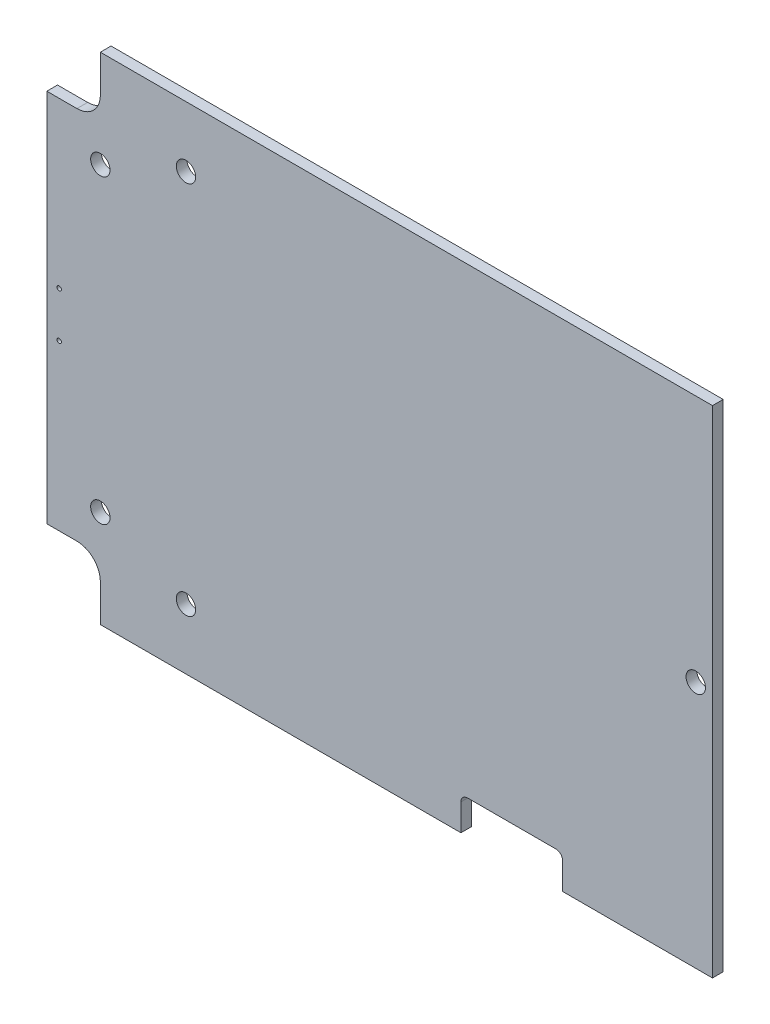
SolidWorks part; units mm, degrees
ref_plane "Płaszczyzna przednia" through (0, 0, 0) normal (0, 0, 1) x (1, 0, 0)
ref_plane "Płaszczyzna górna" through (0, 0, 0) normal (0, 1, 0) x (1, 0, 0)
ref_plane "Płaszczyzna prawa" through (0, 0, 0) normal (1, 0, 0) x (0, 0, -1)
sketch "Sketch1" plane through (0, 0, 0) normal (0, 0, 1) x (1, 0, 0)
  line L7 (246.9504, 63.2305) -> (246.9504, 62.5305) construction
  line L8 (246.9504, 62.5305) -> (245.4504, 62.5305) construction
  line L9 (245.4504, -11.1695) -> (246.9504, -11.1695) construction
  line L10 (246.9504, -11.1695) -> (246.9504, -11.8695) construction
  line L11 (246.9504, -11.8695) -> (393.5004, -11.8695) construction
  line L12 (393.5004, 63.2305) -> (246.9504, 63.2305) construction
  line L13 (245.4504, 62.5305) -> (245.4504, -11.1695) construction
  line L15 (393.5004, -11.8695) -> (393.5004, 63.2305) construction
  line L16 (393.5004, 63.2305) -> (393.5004, 1065.7805) construction
  line L17 (393.5004, -1014.4195) -> (393.5004, -11.8695) construction
  circle A9 centre (347.2504, -2.3195) radius 3 construction
  circle A10 centre (342.9504, 25.6805) radius 2.5 construction
  circle A11 centre (347.2504, 53.6805) radius 3 construction
  circle A12 centre (266.7504, 53.6805) radius 3 construction
  circle A13 centre (253.9504, 48.1805) radius 2.5 construction
  circle A14 centre (266.7504, -2.3195) radius 3 construction
  circle A15 centre (253.9504, 3.1805) radius 2.5 construction
  circle A16 centre (250.4504, -5.8195) radius 3 construction
  circle A17 centre (250.4504, 57.1805) radius 3 construction
  circle A31 centre (375.4504, -5.8195) radius 3 construction
  circle A32 centre (375.4504, -5.8195) radius 1.6 construction
  circle A33 centre (375.4504, 57.1805) radius 3 construction
  circle A34 centre (375.4504, 57.1805) radius 1.6 construction
  circle A35 centre (347.2504, 53.6805) radius 1 construction
  circle A36 centre (342.9504, 25.6805) radius 1 construction
  circle A37 centre (347.2504, -2.3195) radius 1 construction
  circle A38 centre (266.7504, -2.3195) radius 1 construction
  circle A39 centre (253.9504, 3.1805) radius 1 construction
  circle A40 centre (250.4504, -5.8195) radius 1.6 construction
  circle A41 centre (253.9504, 48.1805) radius 1 construction
  circle A42 centre (266.7504, 53.6805) radius 1 construction
  circle A43 centre (250.4504, 57.1805) radius 1.6 construction
sketch "Sketch2" plane through (0, 0, 0) normal (0, 0, 1) x (1, 0, 0)
  line L0 (378.4504, 63.2305) -> (372.4504, 63.2305) construction
  line L1 (372.4504, 63.2305) -> (253.4504, 63.2305) construction
  line L2 (372.4504, -11.8695) -> (378.4504, -11.8695) construction
  line L3 (378.4504, -11.8695) -> (393.5004, -11.8695) construction
  line L4 (246.9504, -11.8695) -> (253.4504, -11.8695) construction
  line L5 (245.4504, -2.8195) -> (245.4504, -11.1695) construction
  line L6 (253.4504, 63.2305) -> (246.9504, 63.2305) construction
  line L7 (245.4504, 62.5305) -> (245.4504, 54.1805) construction
  line L16 (393.5004, 63.2305) -> (246.9504, 63.2305) construction
  line L17 (246.9504, 63.2305) -> (246.9504, 62.5305) construction
  line L18 (246.9504, 62.5305) -> (245.4504, 62.5305) construction
  line L19 (245.4504, 62.5305) -> (245.4504, -11.1695) construction
  line L20 (245.4504, -11.1695) -> (246.9504, -11.1695) construction
  line L21 (246.9504, -11.1695) -> (246.9504, -11.8695) construction
  line L22 (246.9504, -11.8695) -> (393.5004, -11.8695) construction
  line L23 (393.5004, -11.8695) -> (393.5004, 63.2305) construction
  line L24 (393.5004, 63.2305) -> (378.4504, 63.2305) construction
  line L25 (246.9504, 63.2305) -> (246.9504, 62.5305) construction
  line L26 (246.9504, 62.5305) -> (245.4504, 62.5305) construction
  line L27 (245.4504, 54.1805) -> (245.4504, -2.8195) construction
  line L28 (245.4504, -11.1695) -> (246.9504, -11.1695) construction
  line L29 (246.9504, -11.1695) -> (246.9504, -11.8695) construction
  line L30 (253.4504, -11.8695) -> (372.4504, -11.8695) construction
  line L31 (393.5004, -11.8695) -> (393.5004, 63.2305) construction
  line L32 (253.4504, 63.2305) -> (253.4504, 57.1805) construction
  line L33 (250.4504, 54.1805) -> (245.4504, 54.1805) construction
  line L34 (250.4504, -2.8195) -> (245.4504, -2.8195) construction
  line L35 (253.4504, -5.8195) -> (253.4504, -11.8695) construction
  line L36 (372.4504, -5.8195) -> (372.4504, -11.8695) construction
  line L37 (378.4504, -5.8195) -> (378.4504, -11.8695) construction
  line L38 (378.4504, 57.1805) -> (378.4504, 63.2305) construction
  line L39 (372.4504, 57.1805) -> (372.4504, 63.2305) construction
  line L40 (371.9504, 62.7305) -> (253.9504, 62.7305)
  line L41 (253.9504, 62.7305) -> (253.9504, 57.1805)
  line L42 (250.4504, 53.6805) -> (245.9504, 53.6805)
  line L43 (245.9504, 53.6805) -> (245.9504, -2.3195)
  line L44 (250.4504, -2.3195) -> (245.9504, -2.3195)
  line L45 (253.9504, -5.8195) -> (253.9504, -11.3695)
  line L46 (253.9504, -11.3695) -> (371.9504, -11.3695)
  line L47 (371.9504, -5.8195) -> (371.9504, -11.3695)
  line L48 (378.9504, -5.8195) -> (378.9504, -11.3695)
  line L49 (378.9504, -11.3695) -> (393.0004, -11.3695)
  line L50 (393.0004, -11.3695) -> (393.0004, 62.7305)
  line L51 (393.0004, 62.7305) -> (378.9504, 62.7305)
  line L52 (378.9504, 57.1805) -> (378.9504, 62.7305)
  line L53 (371.9504, 57.1805) -> (371.9504, 62.7305)
  circle A0 centre (250.4504, -5.8195) radius 3 construction
  circle A1 centre (375.4504, -5.8195) radius 3 construction
  circle A2 centre (375.4504, 57.1805) radius 3 construction
  circle A3 centre (250.4504, 57.1805) radius 3 construction
  arc A4 (253.4504, -5.8195) -> (250.4504, -2.8195) centre (250.4504, -5.8195) ccw construction
  arc A5 (378.4504, -5.8195) -> (372.4504, -5.8195) centre (375.4504, -5.8195) ccw construction
  arc A6 (372.4504, 57.1805) -> (378.4504, 57.1805) centre (375.4504, 57.1805) ccw construction
  arc A7 (250.4504, 54.1805) -> (253.4504, 57.1805) centre (250.4504, 57.1805) ccw construction
  arc A8 (378.4504, 57.1805) -> (372.4504, 57.1805) centre (375.4504, 57.1805) ccw construction
  arc A9 (372.4504, -5.8195) -> (378.4504, -5.8195) centre (375.4504, -5.8195) ccw construction
  arc A10 (250.4504, -2.8195) -> (253.4504, -5.8195) centre (250.4504, -5.8195) ccw construction
  arc A11 (253.4504, 57.1805) -> (250.4504, 54.1805) centre (250.4504, 57.1805) ccw construction
  arc A12 (250.4504, 53.6805) -> (253.9504, 57.1805) centre (250.4504, 57.1805) ccw
  arc A13 (253.9504, -5.8195) -> (250.4504, -2.3195) centre (250.4504, -5.8195) ccw
  arc A14 (378.9504, -5.8195) -> (371.9504, -5.8195) centre (375.4504, -5.8195) ccw
  arc A15 (371.9504, 57.1805) -> (378.9504, 57.1805) centre (375.4504, 57.1805) ccw
  point P2 (393.5004, 62.7305)
  point P4 (247.4504, 62.7305)
  point P18 (393.0004, -11.8695)
  point P19 (393.0004, 63.2305)
  dimension "D1" = 0.5
extrude "Boss-Extrude1" add sketch "Sketch2" along normal blind 1.6
hole_wizard "M2.5 Clearance Hole1" positions "Sketch3" profile "Sketch4" hole size "M2.5" standard "ISO" end condition through all
sketch "Sketch3" plane through (0, 0, 1.6) normal (0, 0, 1) x (1, 0, 0)
  point P1 (347.2504, -2.3195)
  point P3 (342.9504, 25.6805)
  point P5 (347.2504, 53.6805)
  point P7 (266.7504, -2.3195)
  point P9 (253.9504, 3.1805)
  point P11 (266.7504, 53.6805)
  point P13 (253.9504, 48.1805)
sketch "Sketch4" plane through (347.2504, -2.3195, 1.6) normal (1, 0, 0) x (0, -1, 0)
  line L0 (0, 0) -> (0, 1.6)
  line L1 (0, 1.6) -> (1.45, 1.6)
  line L2 (1.45, 1.6) -> (1.45, 0)
  line L5 (1.45, 0) -> (0, 0)
  line L11 (0, -6.35) -> (0, 107.95) construction
  dimension "Thru Hole Dia." = 2.9
  dimension "Thru Hole Depth" = 1.6
sketch "Sketch5" plane through (0, 0, 1.6) normal (0, 0, 1) x (1, 0, 0)
  line L0 (371.9504, 62.7305) -> (253.9504, 62.7305) construction
  line L1 (393.0004, -11.3695) -> (345.4504, -11.3695)
  line L2 (393.0004, -11.3695) -> (393.0004, 62.7305)
  line L3 (393.0004, 62.7305) -> (345.4504, 62.7305)
  line L4 (345.4504, -11.3695) -> (345.4504, 62.7305)
  line L5 (245.4504, 62.5305) -> (245.4504, -11.1695) construction
  dimension "D1" = 100
extrude "Cut-Extrude1" cut sketch "Sketch5" against normal through all
sketch "Sketch6" plane through (0, 0, 0) normal (0, 0, -1) x (-1, 0, 0)
  circle A0 centre (-247.8005, 29.0805) radius 0.325 construction
  circle A1 centre (-247.8005, 22.2805) radius 0.325 construction
  circle A2 centre (-247.8005, 29.0805) radius 0.325
  circle A3 centre (-247.8005, 22.2805) radius 0.325
extrude "Cut-Extrude2" cut sketch "Sketch6" against normal through all
sketch "Sketch7" plane through (0, 0, 0) normal (0, 0, -1) x (-1, 0, 0)
  line L0 (-307.8504, -7.3695) -> (-307.8504, -12.3195) construction
  line L1 (-323.0504, -12.3195) -> (-323.0504, -7.3695) construction
  line L2 (-322.0504, -6.3695) -> (-308.8504, -6.3695) construction
  line L3 (-307.8504, -7.3695) -> (-307.8504, -12.3195)
  line L4 (-323.0504, -12.3195) -> (-323.0504, -7.3695)
  line L5 (-322.0504, -6.3695) -> (-308.8504, -6.3695)
  line L6 (-307.8504, -12.3195) -> (-323.0504, -12.3195)
  arc A0 (-322.0504, -6.3695) -> (-323.0504, -7.3695) centre (-322.0504, -7.3695) ccw construction
  arc A1 (-307.8504, -7.3695) -> (-308.8504, -6.3695) centre (-308.8504, -7.3695) ccw construction
  arc A2 (-322.0504, -6.3695) -> (-323.0504, -7.3695) centre (-322.0504, -7.3695) ccw
  arc A3 (-307.8504, -7.3695) -> (-308.8504, -6.3695) centre (-308.8504, -7.3695) ccw
extrude "Cut-Extrude3" cut sketch "Sketch7" against normal through all
